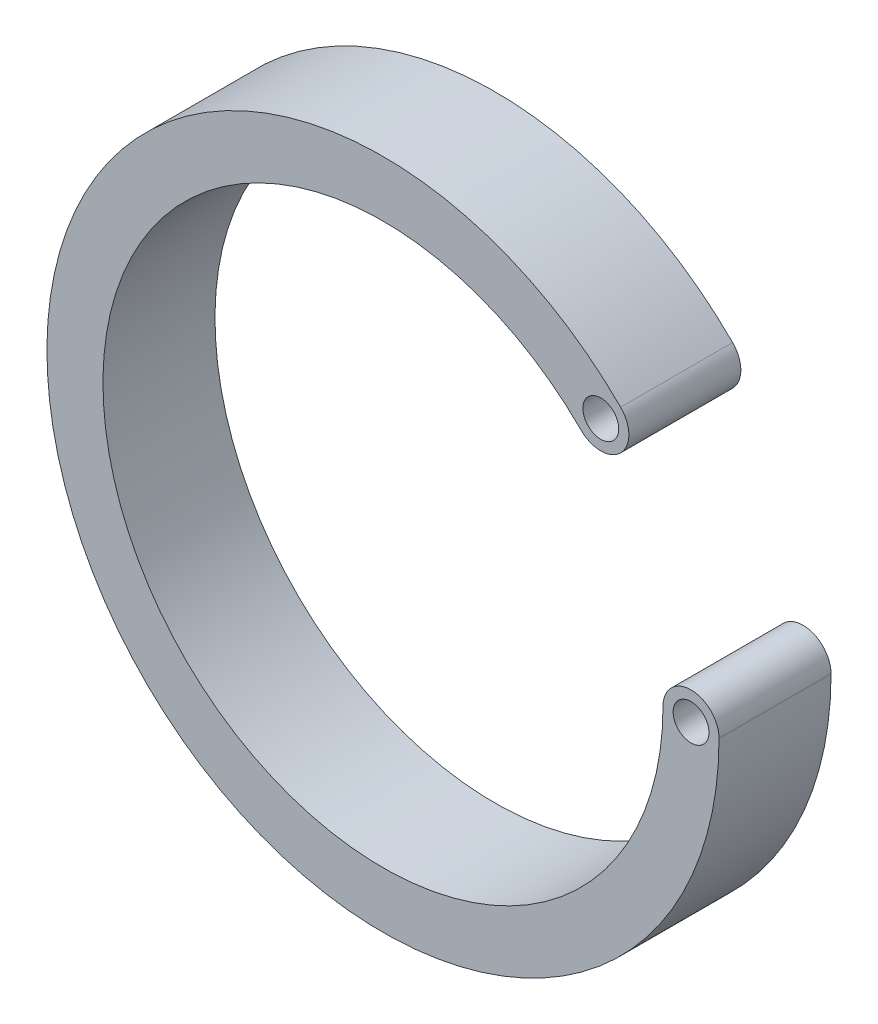
SolidWorks part; units mm, degrees
ref_plane "Front Plane" through (0, 0, 0) normal (0, 0, 1) x (1, 0, 0)
ref_plane "Top Plane" through (0, 0, 0) normal (0, 1, 0) x (1, 0, 0)
ref_plane "Right Plane" through (0, 0, 0) normal (1, 0, 0) x (0, 0, -1)
sketch "Sketch1" plane through (0, 0, 0) normal (0, 0, 1) x (1, 0, 0)
  line L0 (22.4506, 22.4506) -> (26.9408, 26.9408) construction
  line L1 (31.75, 0) -> (38.1, 0) construction
  line L2 (0, 0) -> (31.75, 0) construction
  arc A0 (22.4506, 22.4506) -> (31.75, 0) centre (0, 0) ccw
  arc A1 (26.9408, 26.9408) -> (38.1, 0) centre (0, 0) ccw
  arc A2 (31.75, 0) -> (38.1, 0) centre (34.925, 0) cw
  arc A3 (26.9408, 26.9408) -> (22.4506, 22.4506) centre (24.6957, 24.6957) cw
  circle A4 centre (34.925, 0) radius 2.032
  circle A5 centre (24.6957, 24.6957) radius 2.032
  dimension "D1" = 31.75
  dimension "D2" = 4.064
  dimension "D3" = 38.1
  dimension "D4" = 45
extrude "Boss-Extrude1" add sketch "Sketch1" along normal blind 12.7 contours A3 A1 A2 A0 A5 A4 region at (-30.3288, -12.5626, 0)
equation "\"D3@Sketch1\"=\"D1@Sketch1\"+.25"
